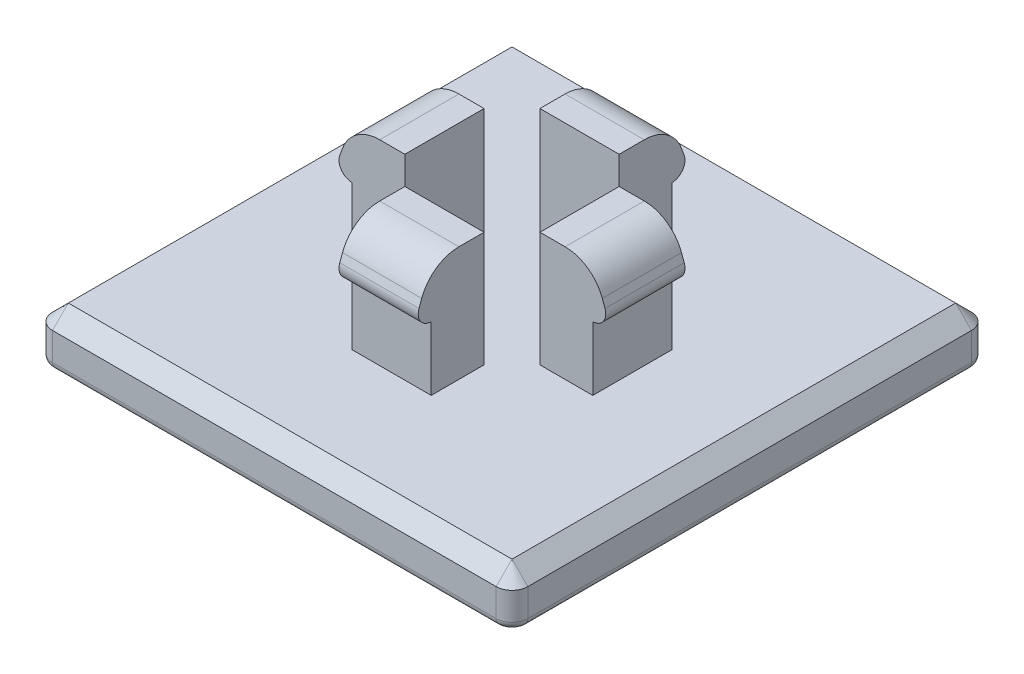
SolidWorks part; units mm, degrees
material "ABS"
ref_plane "Front Plane" through (0, 0, 0) normal (0, 0, 1) x (1, 0, 0)
ref_plane "Top Plane" through (0, 0, 0) normal (0, 1, 0) x (1, 0, 0)
ref_plane "Right Plane" through (0, 0, 0) normal (1, 0, 0) x (0, 0, -1)
sketch "Sketch1" plane through (0, 0, 0) normal (0, 1, 0) x (1, 0, 0)
  line L0 (-7.62, 7.112) -> (-7.62, -7.112)
  line L1 (-7.112, -7.62) -> (7.112, -7.62)
  line L2 (7.62, -7.112) -> (7.62, 7.112)
  line L3 (7.112, 7.62) -> (-7.112, 7.62)
  arc A0 (-7.62, -7.112) -> (-7.112, -7.62) centre (-7.112, -7.112) ccw
  arc A1 (7.112, -7.62) -> (7.62, -7.112) centre (7.112, -7.112) ccw
  arc A2 (7.62, 7.112) -> (7.112, 7.62) centre (7.112, 7.112) ccw
  arc A3 (-7.112, 7.62) -> (-7.62, 7.112) centre (-7.112, 7.112) ccw
  point P37 (0, 0)
  dimension "D1" = 0.508
extrude "Boss-Extrude1" add sketch "Sketch1" along normal blind 1.651
ref_plane "Plane1" through (0, 1.651, 0) normal (0, 1, 0) x (1, 0, 0)
sketch "Sketch3" plane through (0, 1.651, 0) normal (0, 1, 0) x (1, 0, 0)
  line L0 (-3.8605, 1.27) -> (-3.8605, -1.27)
  line L1 (-3.8605, -1.27) -> (-2.1657, -1.27)
  line L2 (-2.1657, -1.27) -> (-2.1657, 1.27)
  line L3 (-2.1657, 1.27) -> (-3.8605, 1.27)
  line L4 (1.27, 2.1657) -> (1.27, 3.8605)
  line L5 (1.27, 3.8605) -> (-1.27, 3.8605)
  line L6 (-1.27, 3.8605) -> (-1.27, 2.1657)
  line L7 (-1.27, 2.1657) -> (1.27, 2.1657)
  line L8 (2.1657, -1.27) -> (3.8605, -1.27)
  line L9 (3.8605, -1.27) -> (3.8605, 1.27)
  line L10 (3.8605, 1.27) -> (2.1657, 1.27)
  line L11 (2.1657, 1.27) -> (2.1657, -1.27)
  line L12 (-1.27, -2.1657) -> (-1.27, -3.8605)
  line L13 (-1.27, -3.8605) -> (1.27, -3.8605)
  line L14 (1.27, -3.8605) -> (1.27, -2.1657)
  line L15 (1.27, -2.1657) -> (-1.27, -2.1657)
  circle A0 centre (0, 0) radius 4.064
  point P22 (0, 0)
  dimension "D1" = 2.54
  dimension "D2" = 8.128
  dimension "D3" = 4
extrude "Boss-Extrude2" add sketch "Sketch3" along normal blind 3.683 contours L6 L7 L4 L5 | L10 L11 L8 L9 | L14 L15 L12 L13 | L2 L3 L0 L1 region at (-3.0131, 1.651, 0) region at (0, 1.651, -3.0131) region at (0, 1.651, 3.0131) region at (3.0131, 1.651, 0)
sketch "Sketch4" plane through (0, 0, 0) normal (0, 0, 1) x (1, 0, 0)
  line L0 (0, 7.0102) -> (0, 4.4783) construction
  line L1 (-3.8605, 5.334) -> (-4.2514, 4.2599)
  line L2 (3.8605, 5.334) -> (4.2514, 4.2599)
  line L4 (-3.8605, 5.334) -> (-3.8605, 1.651) construction
  line L5 (-3.8605, 3.7016) -> (-3.8605, 5.334)
  line L6 (3.8605, 3.7016) -> (3.8605, 5.334)
  arc A0 (-4.2514, 4.2599) -> (-3.8605, 3.7016) centre (-3.8605, 4.1176) ccw
  arc A1 (4.2514, 4.2599) -> (3.8605, 3.7016) centre (3.8605, 4.1176) cw
extrude "Boss-Extrude3" add sketch "Sketch4" along normal mid plane 2.54
sketch "Sketch5" plane through (0, 0, 0) normal (1, 0, 0) x (0, 0, -1)
  line L0 (0, 6.7375) -> (0, 2.9007) construction
  line L1 (-3.8605, 5.334) -> (-4.2514, 4.2599)
  line L2 (3.8605, 5.334) -> (4.2514, 4.2599)
  line L3 (-3.8605, 5.334) -> (-3.8605, 1.651) construction
  line L4 (-3.8605, 5.334) -> (-3.8605, 3.6992)
  line L5 (3.8605, 5.334) -> (3.8605, 3.6992)
  line L6 (8.382, 1.651) -> (-8.382, 1.651) construction
  arc A0 (-4.2514, 4.2599) -> (-3.8605, 3.6992) centre (-3.8588, 4.117) ccw
  arc A1 (4.2514, 4.2599) -> (3.8605, 3.6992) centre (3.8588, 4.117) cw
  dimension "D1" = 2.0482
extrude "Boss-Extrude4" add sketch "Sketch5" along normal mid plane 2.54
fillet "Fillet1" radius 1.27 4 edges at (0, 5.334, 3.8605) (3.8605, 5.334, 0) (0, 5.334, -3.8605) (-3.8605, 5.334, 0)
chamfer "Chamfer1" distance 0.508 angle 45 8 edges at (-7.62, 1.651, 0) (-7.4712, 1.651, 7.4712) (-7.4712, 1.651, -7.4712) (0, 1.651, 7.62) (0, 1.651, -7.62) (7.4712, 1.651, 7.4712) (7.4712, 1.651, -7.4712) (7.62, 1.651, 0)
fillet "Fillet2" radius 0.254 8 edges at (7.4712, 0, 7.4712) (0, 0, 7.62) (-7.4712, 0, 7.4712) (-7.62, 0, 0) (-7.4712, 0, -7.4712) (0, 0, -7.62) (7.4712, 0, -7.4712) (7.62, 0, 0)
